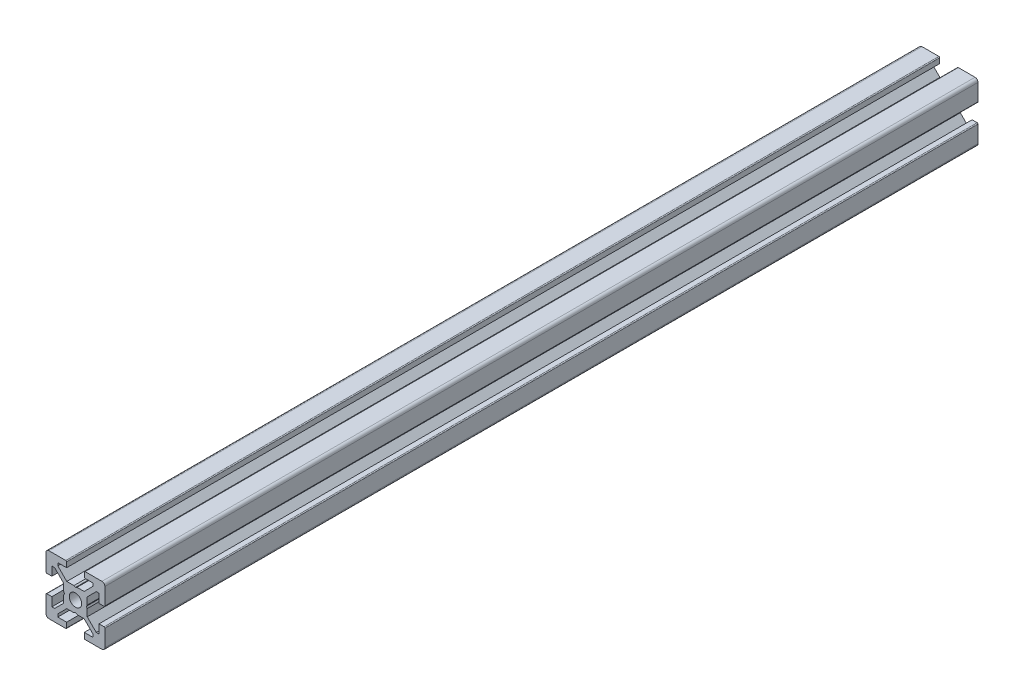
SolidWorks part; units mm, degrees
ref_plane "Front Plane" through (0, 0, 0) normal (0, 0, 1) x (1, 0, 0)
ref_plane "Top Plane" through (0, 0, 0) normal (0, 1, 0) x (1, 0, 0)
ref_plane "Right Plane" through (0, 0, 0) normal (1, 0, 0) x (0, 0, -1)
ref_plane "Plane1" through (0, 0, 0) normal (0, 0, 1) x (1, 0, 0)
sketch "Sketch1" plane through (0, 0, 0) normal (0, 0, 1) x (1, 0, 0)
  line L0 (-10, 9) -> (-10, 3.3)
  line L1 (-9.7, 3) -> (-8, 3)
  line L2 (-8, 3) -> (-8, 6)
  line L3 (-8, 6) -> (-7.0607, 6)
  line L4 (-7.0607, 6) -> (-4, 2.9393)
  line L5 (-4, 2.9393) -> (-4, 0.5196)
  line L6 (-4, 0.5196) -> (-3.7, 0)
  line L7 (-3.7, 0) -> (-4, -0.5196)
  line L8 (-4, -0.5196) -> (-4, -2.9393)
  line L9 (-4, -2.9393) -> (-7.0607, -6)
  line L10 (-7.0607, -6) -> (-8, -6)
  line L11 (-8, -6) -> (-8, -3)
  line L12 (-8, -3) -> (-9.7, -3)
  line L13 (-10, -3.3) -> (-10, -9)
  line L14 (-9, -10) -> (-3.3, -10)
  line L15 (-3, -9.7) -> (-3, -8)
  line L16 (-3, -8) -> (-6, -8)
  line L17 (-6, -8) -> (-6, -7.0607)
  line L18 (-6, -7.0607) -> (-2.9393, -4)
  line L19 (-2.9393, -4) -> (-0.5196, -4)
  line L20 (-0.5196, -4) -> (0, -3.7)
  line L21 (0, -3.7) -> (0.5196, -4)
  line L22 (0.5196, -4) -> (2.9393, -4)
  line L23 (2.9393, -4) -> (6, -7.0607)
  line L24 (6, -7.0607) -> (6, -8)
  line L25 (6, -8) -> (3, -8)
  line L26 (3, -8) -> (3, -9.7)
  line L27 (3.3, -10) -> (9, -10)
  line L28 (10, -9) -> (10, -3.3)
  line L29 (9.7, -3) -> (8, -3)
  line L30 (8, -3) -> (8, -6)
  line L31 (8, -6) -> (7.0606, -6)
  line L32 (7.0606, -6) -> (4, -2.9393)
  line L33 (4, -2.9393) -> (4, -0.5196)
  line L34 (4, -0.5196) -> (3.7, 0)
  line L35 (3.7, 0) -> (4, 0.5196)
  line L36 (4, 0.5196) -> (4, 2.9393)
  line L37 (4, 2.9393) -> (7.0607, 6)
  line L38 (7.0607, 6) -> (8, 6)
  line L39 (8, 6) -> (8, 3)
  line L40 (8, 3) -> (9.7, 3)
  line L41 (10, 3.3) -> (10, 9)
  line L42 (9, 10) -> (3.3, 10)
  line L43 (3, 9.7) -> (3, 8)
  line L44 (3, 8) -> (6, 8)
  line L45 (6, 8) -> (6, 7.0607)
  line L46 (6, 7.0607) -> (2.9393, 4)
  line L47 (2.9393, 4) -> (0.5196, 4)
  line L48 (0.5196, 4) -> (0, 3.7)
  line L49 (0, 3.7) -> (-0.5196, 4)
  line L50 (-0.5196, 4) -> (-2.9394, 4)
  line L51 (-2.9394, 4) -> (-6, 7.0606)
  line L52 (-6, 7.0606) -> (-6, 8)
  line L53 (-6, 8) -> (-3, 8)
  line L54 (-3, 8) -> (-3, 9.7)
  line L55 (-3.3, 10) -> (-9, 10)
  arc A0 (-10, 3.3) -> (-9.7, 3) centre (-9.7, 3.3) ccw
  arc A1 (-9.7, -3) -> (-10, -3.3) centre (-9.7, -3.3) ccw
  arc A2 (-10, -9) -> (-9, -10) centre (-9, -9) ccw
  arc A3 (-3.3, -10) -> (-3, -9.7) centre (-3.3, -9.7) ccw
  arc A4 (3, -9.7) -> (3.3, -10) centre (3.3, -9.7) ccw
  arc A5 (9, -10) -> (10, -9) centre (9, -9) ccw
  arc A6 (10, -3.3) -> (9.7, -3) centre (9.7, -3.3) ccw
  arc A7 (9.7, 3) -> (10, 3.3) centre (9.7, 3.3) ccw
  arc A8 (10, 9) -> (9, 10) centre (9, 9) ccw
  arc A9 (3.3, 10) -> (3, 9.7) centre (3.3, 9.7) ccw
  arc A10 (-3, 9.7) -> (-3.3, 10) centre (-3.3, 9.7) ccw
  arc A11 (-9, 10) -> (-10, 9) centre (-9, 9) ccw
extrude "Boss-Extrude1" add sketch "Sketch1" against normal blind 296.5
ref_plane "Plane2" through (0, 0, 0) normal (1, 0, 0) x (0, 0, -1)
sketch "Sketch2" plane through (0, 0, 0) normal (1, 0, 0) x (0, 0, -1)
  line L0 (0, 0) -> (0, 2.1)
  line L1 (0, 2.1) -> (355, 2.1)
  line L2 (355, 2.1) -> (355, 0)
  line L3 (355, 0) -> (0, 0)
  line L4 (355, 0) -> (0, 0) construction
revolve "Cut-Revolve1" cut sketch "Sketch2" angle 360 about L4 reverse direction yes
ref_plane "Plane3" through (0, 0, 0) normal (1, 0, 0) x (0, 0, -1)
sketch "Sketch3" plane through (0, 0, 0) normal (1, 0, 0) x (0, 0, -1)
  circle A0 centre (177.5, 0) radius 3.6751
extrude "Cut-Extrude1" [suppressed] cut sketch "Sketch3" against normal blind 10 and the other way blind 10
ref_plane "Plane4" through (0, 0, -148.25) normal (0, 0, 1) x (1, 0, 0)
